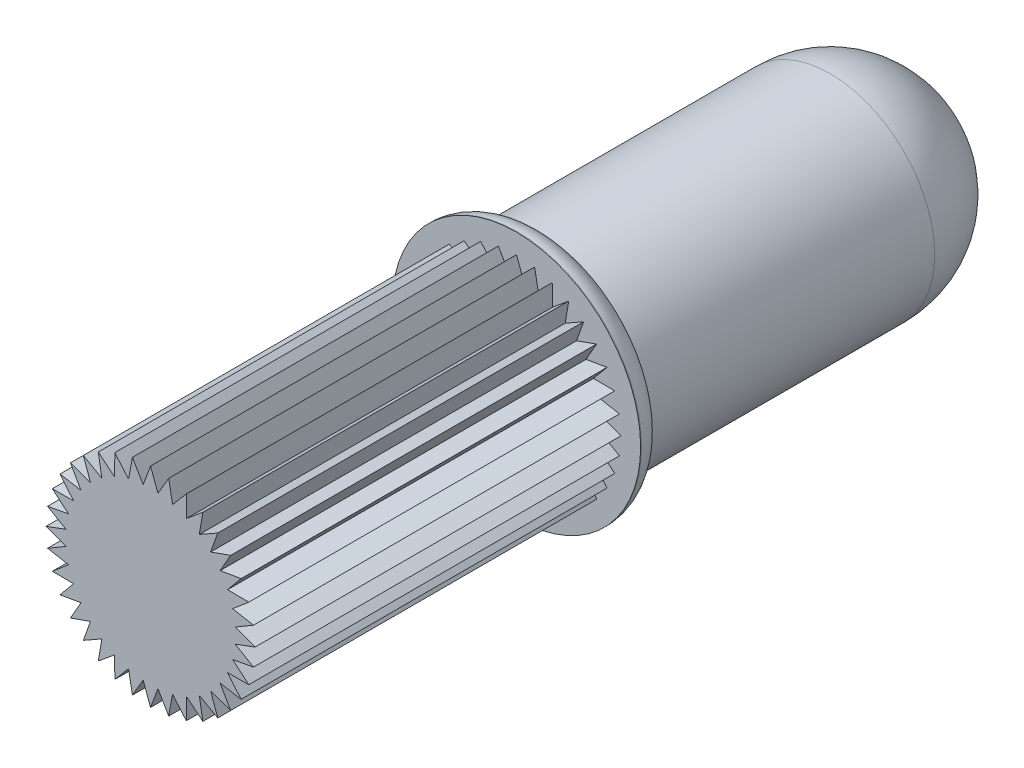
SolidWorks part; units mm, degrees
material "Brass"
ref_plane "Front Plane" through (0, 0, 0) normal (0, 0, 1) x (1, 0, 0)
ref_plane "Top Plane" through (0, 0, 0) normal (0, 1, 0) x (1, 0, 0)
ref_plane "Right Plane" through (0, 0, 0) normal (1, 0, 0) x (0, 0, -1)
ref_plane "Plane1" through (0, 0, 15) normal (0, 0, 1) x (1, 0, 0)
sketch "Sketch1" plane through (0, 0, 0) normal (0, 0, 1) x (1, 0, 0)
  circle A0 centre (0, 0) radius 4
  dimension "D1" = 8
extrude "Extrude1" add sketch "Sketch1" along normal blind 30
fillet "Fillet1" radius 4 1 edges at (4, 0, 0)
sketch "Sketch2" plane through (0, 0, 15) normal (0, 0, 1) x (1, 0, 0)
  circle A0 centre (0, 0) radius 4.75
  circle A1 centre (0, 0) radius 4 construction
  dimension "D1" = 0.75
extrude "Extrude2" add sketch "Sketch2" along normal blind 1
fillet "Fillet2" radius 1 1 edges at (4.75, 0, 15)
sketch "Sketch3" plane through (0, 0, 30) normal (0, 0, 1) x (1, 0, 0)
  line L0 (0, 0) -> (0, 5.3545) construction
  line L1 (0, 4) -> (-0.2833, 3.2376)
  line L2 (0, 4) -> (0.2833, 3.2376)
  line L3 (0, 0) -> (-0.2833, 3.2376) construction
  line L4 (0.6946, 3.9392) -> (0.8412, 3.1393)
  line L5 (0.6946, 3.9392) -> (0.2833, 3.2376)
  line L6 (1.3681, 3.7588) -> (1.3735, 2.9455)
  line L7 (1.3681, 3.7588) -> (0.8412, 3.1393)
  line L8 (2, 3.4641) -> (1.8641, 2.6622)
  line L9 (2, 3.4641) -> (1.3735, 2.9455)
  line L10 (2.5712, 3.0642) -> (2.2981, 2.2981)
  line L11 (2.5712, 3.0642) -> (1.8641, 2.6622)
  line L12 (3.0642, 2.5712) -> (2.6622, 1.8641)
  line L13 (3.0642, 2.5712) -> (2.2981, 2.2981)
  line L14 (3.4641, 2) -> (2.9455, 1.3735)
  line L15 (3.4641, 2) -> (2.6622, 1.8641)
  line L16 (3.7588, 1.3681) -> (3.1393, 0.8412)
  line L17 (3.7588, 1.3681) -> (2.9455, 1.3735)
  line L18 (3.9392, 0.6946) -> (3.2376, 0.2833)
  line L19 (3.9392, 0.6946) -> (3.1393, 0.8412)
  line L20 (4, 0) -> (3.2376, -0.2833)
  line L21 (4, 0) -> (3.2376, 0.2833)
  line L22 (3.9392, -0.6946) -> (3.1393, -0.8412)
  line L23 (3.9392, -0.6946) -> (3.2376, -0.2833)
  line L24 (3.7588, -1.3681) -> (2.9455, -1.3735)
  line L25 (3.7588, -1.3681) -> (3.1393, -0.8412)
  line L26 (3.4641, -2) -> (2.6622, -1.8641)
  line L27 (3.4641, -2) -> (2.9455, -1.3735)
  line L28 (3.0642, -2.5712) -> (2.2981, -2.2981)
  line L29 (3.0642, -2.5712) -> (2.6622, -1.8641)
  line L30 (2.5712, -3.0642) -> (1.8641, -2.6622)
  line L31 (2.5712, -3.0642) -> (2.2981, -2.2981)
  line L32 (2, -3.4641) -> (1.3735, -2.9455)
  line L33 (2, -3.4641) -> (1.8641, -2.6622)
  line L34 (1.3681, -3.7588) -> (0.8412, -3.1393)
  line L35 (1.3681, -3.7588) -> (1.3735, -2.9455)
  line L36 (0.6946, -3.9392) -> (0.2833, -3.2376)
  line L37 (0.6946, -3.9392) -> (0.8412, -3.1393)
  line L38 (0, -4) -> (-0.2833, -3.2376)
  line L39 (0, -4) -> (0.2833, -3.2376)
  line L40 (-0.6946, -3.9392) -> (-0.8412, -3.1393)
  line L41 (-0.6946, -3.9392) -> (-0.2833, -3.2376)
  line L42 (-1.3681, -3.7588) -> (-1.3735, -2.9455)
  line L43 (-1.3681, -3.7588) -> (-0.8412, -3.1393)
  line L44 (-2, -3.4641) -> (-1.8641, -2.6622)
  line L45 (-2, -3.4641) -> (-1.3735, -2.9455)
  line L46 (-2.5712, -3.0642) -> (-2.2981, -2.2981)
  line L47 (-2.5712, -3.0642) -> (-1.8641, -2.6622)
  line L48 (-3.0642, -2.5712) -> (-2.6622, -1.8641)
  line L49 (-3.0642, -2.5712) -> (-2.2981, -2.2981)
  line L50 (-3.4641, -2) -> (-2.9455, -1.3735)
  line L51 (-3.4641, -2) -> (-2.6622, -1.8641)
  line L52 (-3.7588, -1.3681) -> (-3.1393, -0.8412)
  line L53 (-3.7588, -1.3681) -> (-2.9455, -1.3735)
  line L54 (-3.9392, -0.6946) -> (-3.2376, -0.2833)
  line L55 (-3.9392, -0.6946) -> (-3.1393, -0.8412)
  line L56 (-4, 0) -> (-3.2376, 0.2833)
  line L57 (-4, 0) -> (-3.2376, -0.2833)
  line L58 (-3.9392, 0.6946) -> (-3.1393, 0.8412)
  line L59 (-3.9392, 0.6946) -> (-3.2376, 0.2833)
  line L60 (-3.7588, 1.3681) -> (-2.9455, 1.3735)
  line L61 (-3.7588, 1.3681) -> (-3.1393, 0.8412)
  line L62 (-3.4641, 2) -> (-2.6622, 1.8641)
  line L63 (-3.4641, 2) -> (-2.9455, 1.3735)
  line L64 (-3.0642, 2.5712) -> (-2.2981, 2.2981)
  line L65 (-3.0642, 2.5712) -> (-2.6622, 1.8641)
  line L66 (-2.5712, 3.0642) -> (-1.8641, 2.6622)
  line L67 (-2.5712, 3.0642) -> (-2.2981, 2.2981)
  line L68 (-2, 3.4641) -> (-1.3735, 2.9455)
  line L69 (-2, 3.4641) -> (-1.8641, 2.6622)
  line L70 (-1.3681, 3.7588) -> (-0.8412, 3.1393)
  line L71 (-1.3681, 3.7588) -> (-1.3735, 2.9455)
  line L72 (-0.6946, 3.9392) -> (-0.2833, 3.2376)
  line L73 (-0.6946, 3.9392) -> (-0.8412, 3.1393)
  circle A0 centre (0, 0) radius 3.25 construction
  circle A1 centre (0, 0) radius 4 construction
  circle A2 centre (0, 0) radius 4 construction
  circle A3 centre (0, 0) radius 4 construction
  dimension "D1" = 0.75
  dimension "D2" = 5
extrude "Extrude4" cut sketch "Sketch3" against normal up to surface (14 mm away) flip side to cut up to face at (4.75, 0, 16)
